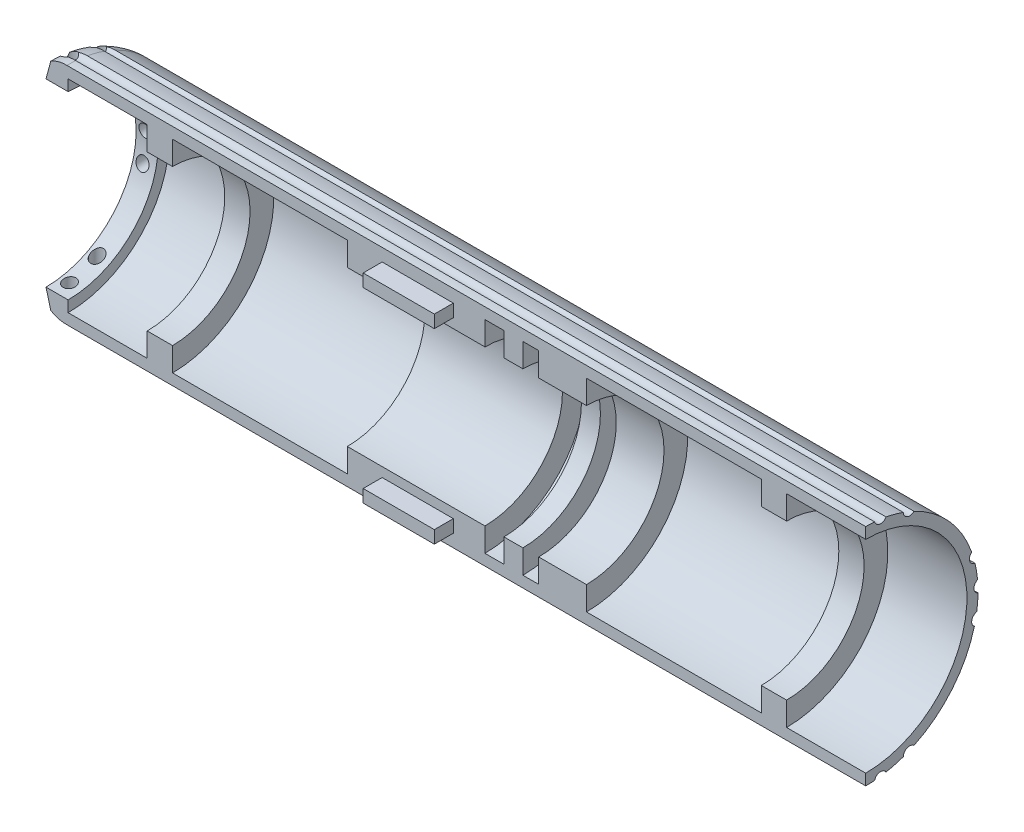
SolidWorks part; units mm, degrees
ref_plane "Front Plane" through (0, 0, 0) normal (0, 0, 1) x (1, 0, 0)
ref_plane "Top Plane" through (0, 0, 0) normal (0, 1, 0) x (1, 0, 0)
ref_plane "Right Plane" through (0, 0, 0) normal (1, 0, 0) x (0, 0, -1)
sketch "Sketch1" plane through (0, 0, 0) normal (0, 0, 1) x (1, 0, 0)
  line L1 (-17.1588, 0) -> (33.3396, 0)
  line L5 (33.3396, 0.7) -> (28.3396, 0.7)
  line L6 (28.3396, 0.7) -> (28.3396, 2.2)
  line L7 (28.3396, 2.2) -> (26.7396, 2.2)
  line L8 (26.7396, 2.2) -> (26.7396, 0.7)
  line L9 (26.7396, 0.7) -> (15.6896, 0.7)
  line L10 (15.6896, 0.7) -> (15.6896, 2.2)
  line L11 (15.6896, 2.2) -> (12.6696, 2.2)
  line L12 (12.6696, 2.2) -> (12.6696, 0.7)
  line L13 (12.6696, 0.7) -> (11.6696, 0.7)
  line L14 (11.6696, 0.7) -> (11.6696, 2.2)
  line L15 (11.6696, 2.2) -> (10.4696, 2.2)
  line L16 (10.4696, 2.2) -> (10.4696, 0.7)
  line L17 (10.4696, 0.7) -> (9.2696, 0.7)
  line L18 (9.2696, 0.7) -> (9.2696, 2.2)
  line L19 (9.2696, 2.2) -> (0.5696, 2.2)
  line L20 (0.5696, 2.2) -> (0.5696, 0.7)
  line L21 (0.5696, 0.7) -> (-10.4804, 0.7)
  line L22 (-10.4804, 0.7) -> (-10.4804, 2.2)
  line L23 (-10.4804, 2.2) -> (-12.0804, 2.2)
  line L24 (-12.0804, 2.2) -> (-12.0804, 0.7)
  line L25 (-12.0804, 0.7) -> (-17.0804, 0.7)
  line L30 (-19.05, 7.1) -> (26.85, 7.1) construction
  line L31 (-17.0804, 0.7) -> (-17.0804, 1.4)
  line L44 (-18.4804, 2.6794) -> (-18.4804, -5.4306) construction
  line L45 (-18.4804, 1.4) -> (-18.1804, 0.2804)
  line L46 (-17.0804, 1.4) -> (-18.4804, 1.4)
  line L47 (33.3396, 0.7) -> (33.3396, 0)
  arc A1 (-17.1588, 0) -> (-18.1804, 0.2804) centre (-17.2142, 1.7991) cw
  point P0 (33.641, 0)
  dimension "D24" = 1.8
  dimension "D2" = 0.7
  dimension "D3" = 0.7
  dimension "D4" = 0.7
  dimension "D5" = 0.7
  dimension "D6" = 0.7
  dimension "D8" = 5
  dimension "D9" = 1.6
  dimension "D10" = 11.05
  dimension "D11" = 6.4
  dimension "D12" = 3.02
  dimension "D13" = 1
  dimension "D14" = 1.2
  dimension "D15" = 1.2
  dimension "D16" = 8.7
  dimension "D17" = 11.05
  dimension "D18" = 1.6
  dimension "D19" = 5
  dimension "D20" = 0.7
  dimension "D21" = 1.5
  dimension "D22" = 1.4
  dimension "D23" = 105
  dimension "D25" = 0.3
revolve "Revolve1" add sketch "Sketch1" angle 180 about L30
sketch "Sketch3" plane through (0, 0, 0) normal (0, 0, 1) x (1, 0, 0)
  line L1 (2.7696, 13.4) -> (7.2696, 13.4)
  line L2 (2.7696, 13.4) -> (2.7696, 12.6)
  line L3 (2.7696, 12.6) -> (7.2696, 12.6)
  line L4 (7.2696, 13.4) -> (7.2696, 12.6)
  line L5 (2.7696, 1.6) -> (7.2696, 1.6)
  line L6 (2.7696, 1.6) -> (2.7696, 0.8)
  line L7 (2.7696, 0.8) -> (7.2696, 0.8)
  line L8 (7.2696, 1.6) -> (7.2696, 0.8)
  line L9 (0.5696, 13.5) -> (0.5696, 0.7) construction
  line L11 (-17.1588, 0) -> (33.3396, 0) construction
  line L12 (-17.1588, 14.2) -> (33.3396, 14.2) construction
  line L13 (0.5696, 2.2) -> (0.5696, 0.7) construction
  dimension "D1" = 4.5
  dimension "D2" = 0.8
  dimension "D3" = 2.2
  dimension "D4" = 4.5
  dimension "D5" = 0.8
  dimension "D6" = 2.2
  dimension "D7" = 0.8
  dimension "D8" = 0.8
sketch "Sketch4" plane through (0, 0, 0) normal (1, 0, 0) x (0, 0, -1)
  line L0 (0, 12) -> (0, 2.2) construction
  line L1 (0, 7.1) -> (0.9463, -0.088) construction
  line L2 (0, 7.1) -> (0.9463, 14.288) construction
  line L3 (0, 7.1) -> (2.7745, 13.7981) construction
  line L4 (0, 7.1) -> (6.9578, 9.1376) construction
  line L6 (0, 7.1) -> (7.244, 7.3938) construction
  line L7 (0, 7.1) -> (2.7745, 0.4019) construction
  line L8 (0, 7.1) -> (15.7741, 7.1) construction
  line L9 (7.0999, 5.6326) -> (0, 7.1) construction
  circle A0 centre (0.9463, 14.288) radius 0.4
  circle A1 centre (7.0999, 5.6326) radius 0.4
  circle A2 centre (2.7745, 13.7981) radius 0.4
  circle A3 centre (6.9578, 9.1376) radius 0.4
  circle A5 centre (7.244, 7.3938) radius 0.4
  circle A6 centre (2.7745, 0.4019) radius 0.4
  circle A9 centre (0.9463, -0.088) radius 0.4
  point P18 (0, 0)
  point P19 (0, 0)
  dimension "D7" = 0.8
  dimension "D8" = 0.8
  dimension "D9" = 0.8
  dimension "D10" = 0.8
  dimension "D11" = 0.8
  dimension "D12" = 0.8
  dimension "D20" = 0.8
  dimension "D1" = 7.5
  dimension "D2" = 15
  dimension "D3" = 7.5
  dimension "D4" = 14
  dimension "D5" = 7.25
  dimension "D6" = 15
  dimension "D13" = 4.9
  dimension "D14" = 7.25
  dimension "D15" = 7.25
  dimension "D16" = 7.25
  dimension "D17" = 7.25
  dimension "D18" = 7.25
  dimension "D19" = 7.25
  dimension "D21" = 14
extrude "Cut-Extrude2" cut sketch "Sketch4" against normal blind 18
extrude "Cut-Extrude3" cut sketch "Sketch4<2>" along normal blind 40
sketch "Sketch4<2>" plane through (0, 0, 0) normal (1, 0, 0) x (0, 0, -1) same geometry as "Sketch4"
ref_plane "Plane1" through (-17.9, 0, 0) normal (-1, 0, 0) x (0, 0, 1)
sketch "Sketch5" plane through (-17.9, 0, 0) normal (-1, 0, 0) x (0, 0, 1)
  line L0 (0, 15.2573) -> (0, -1.603) construction
  line L1 (-0.9033, 13.9611) -> (-0.9033, 7.9742) construction
  line L33 (-0.5134, 11.6922) -> (-0.9134, 11.6922)
  line L34 (-0.5134, 11.6922) -> (-0.5134, 14.6922)
  line L35 (-0.5134, 14.6922) -> (-0.9134, 14.6922)
  line L36 (-0.9134, 11.6922) -> (-0.9134, 14.6922)
  arc A0 (-0.6835, 13.9865) -> (-1.1222, 13.9287) centre (0, 7.1) ccw construction
  dimension "D1" = 0.4
  dimension "D2" = 3
revolve "Cut-Revolve1" cut sketch "Sketch5" angle 360 about L36
sketch "Sketch6" plane through (-17.9, 0, 0) normal (-1, 0, 0) x (0, 0, 1)
  line L0 (-2.6483, 13.4935) -> (-2.6483, 8.8337) construction
  line L6 (-2.2779, 10.9006) -> (-2.6779, 10.9006)
  line L7 (-2.2779, 10.9006) -> (-2.2779, 14.5851)
  line L8 (-2.2779, 14.5851) -> (-2.6779, 14.5851)
  line L9 (-2.6779, 10.9006) -> (-2.6779, 14.5851)
  arc A0 (-2.4425, 13.5749) -> (-2.8513, 13.4056) centre (0, 7.1) ccw construction
  dimension "D1" = 0.4
revolve "Cut-Revolve2" cut sketch "Sketch6" angle 360 about L9
sketch "Sketch7" plane through (-17.9, 0, 0) normal (-1, 0, 0) x (0, 0, 1)
  line L0 (-6.6414, 9.0449) -> (-1.4409, 9.0449) construction
  line L6 (-4.4604, 8.6449) -> (-7.6237, 8.6449)
  line L7 (-4.4604, 8.6449) -> (-4.4604, 9.0449)
  line L8 (-4.4604, 9.0449) -> (-7.6237, 9.0449)
  line L9 (-7.6237, 8.6449) -> (-7.6237, 9.0449)
  arc A0 (-6.5758, 9.2562) -> (-6.7002, 8.8316) centre (0, 7.1) ccw construction
  dimension "D1" = 0.4
  dimension "D2" = 0
revolve "Cut-Revolve3" cut sketch "Sketch7" angle 360 about L0
sketch "Sketch8" plane through (-17.9, 0, 0) normal (-1, 0, 0) x (0, 0, 1)
  line L0 (-6.9146, 7.3804) -> (-2.348, 7.1952) construction
  line L6 (-7.6561, 7.8) -> (-4.7556, 7.8)
  line L7 (-7.6561, 7.8) -> (-7.6561, 7.4)
  line L8 (-7.6561, 7.4) -> (-4.7556, 7.4)
  line L9 (-4.7556, 7.8) -> (-4.7556, 7.4)
  arc A0 (-6.9021, 7.6014) -> (-6.92, 7.1592) centre (0, 7.1) ccw construction
  dimension "D1" = 0.4
revolve "Cut-Revolve4" cut sketch "Sketch8" angle 360 about L8
sketch "Sketch9" plane through (-17.9, 0, 0) normal (-1, 0, 0) x (0, 0, 1)
  line L0 (-2.6483, 0.7065) -> (-2.6483, 8.6726) construction
  line L6 (-3.0483, 0.2343) -> (-2.6483, 0.2343)
  line L7 (-3.0483, 0.2343) -> (-3.0483, 3.6343)
  line L8 (-3.0483, 3.6343) -> (-2.6483, 3.6343)
  line L9 (-2.6483, 0.2343) -> (-2.6483, 3.6343)
  arc A0 (-2.8513, 0.7944) -> (-2.4425, 0.6251) centre (0, 7.1) ccw construction
  dimension "D1" = 0.4
revolve "Cut-Revolve5" cut sketch "Sketch9" angle 360 about L0
sketch "Sketch10" plane through (-17.9, 0, 0) normal (-1, 0, 0) x (0, 0, 1)
  line L0 (-0.9033, 0.2389) -> (-0.9033, 10.6809) construction
  line L6 (-1.3033, 0) -> (-0.9033, 0)
  line L7 (-1.3033, 0) -> (-1.3033, 4.4235)
  line L8 (-1.3033, 4.4235) -> (-0.9033, 4.4235)
  line L9 (-0.9033, 0) -> (-0.9033, 4.4235)
  arc A0 (-1.1222, 0.2713) -> (-0.6835, 0.2135) centre (0, 7.1) ccw construction
  dimension "D1" = 0.4
revolve "Cut-Revolve6" cut sketch "Sketch10" angle 360 about L0
sketch "Sketch11" plane through (-17.9, 0, 0) normal (-1, 0, 0) x (0, 0, 1)
  line L0 (-6.7771, 5.6993) -> (0.1736, 5.6993) construction
  line L2 (-7.6678, 6.0993) -> (-4.263, 6.0993)
  line L3 (-7.6678, 6.0993) -> (-7.6678, 5.6993)
  line L4 (-7.6678, 5.6993) -> (-4.263, 5.6993)
  line L5 (-4.263, 6.0993) -> (-4.263, 5.6993)
  arc A0 (-6.8184, 5.9167) -> (-6.7288, 5.4834) centre (0, 7.1) ccw construction
  dimension "D1" = 0.4
revolve "Cut-Revolve7" cut sketch "Sketch11" angle 360 about L0
extrude "Boss-Extrude1" add sketch "Sketch3" along normal blind 1.2
